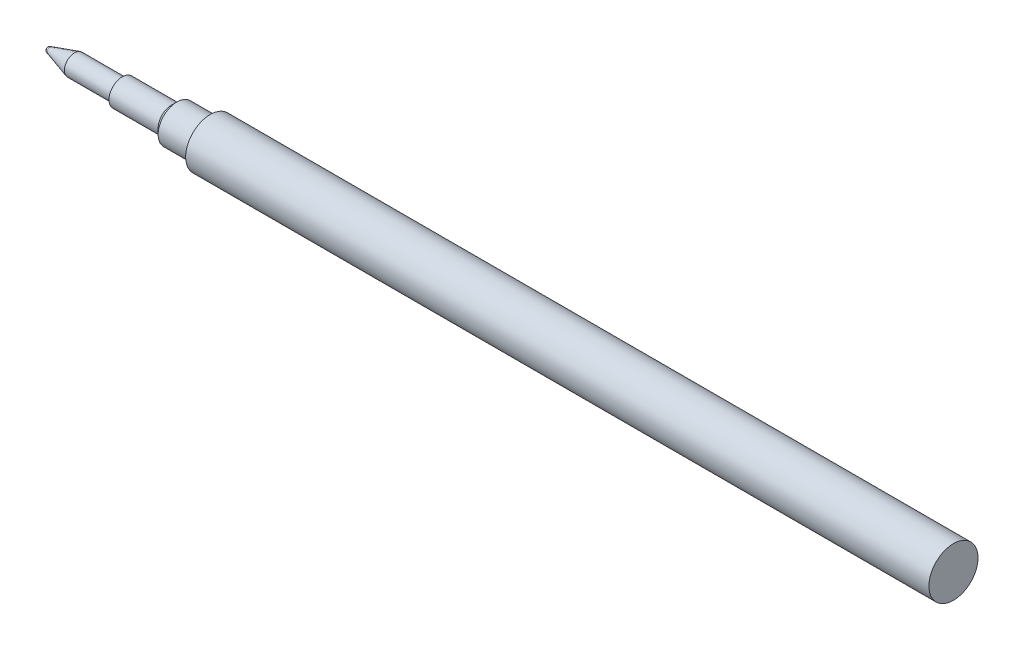
SolidWorks part; units mm, degrees
ref_plane "Front Plane" through (0, 0, 0) normal (0, 0, 1) x (1, 0, 0)
ref_plane "Top Plane" through (0, 0, 0) normal (0, 1, 0) x (1, 0, 0)
ref_plane "Right Plane" through (0, 0, 0) normal (1, 0, 0) x (0, 0, -1)
sketch "Sketch1" plane through (0, 0, 0) normal (0, 0, 1) x (1, 0, 0)
  line L0 (-90.77, 0) -> (-94.83, 0)
  line L1 (0, 0) -> (-90.77, 0)
  line L2 (0, 0) -> (0, 3)
  line L3 (0, 3) -> (-90.77, 3)
  line L4 (-90.77, 0) -> (-90.77, 3)
  line L5 (-94.83, 0) -> (-94.83, 2.3)
  line L6 (-94.83, 2.3) -> (-90.77, 2.3)
  line L7 (-94.83, 0) -> (-95.51, 0)
  line L8 (-95.51, 0) -> (-95.51, 1.62)
  line L9 (-95.51, 1.62) -> (-94.83, 2.3)
  line L10 (-95.51, 0) -> (-101.51, 0)
  line L11 (-101.51, 0) -> (-101.51, 1.62)
  line L12 (-101.51, 1.62) -> (-95.51, 1.62)
  line L13 (-101.51, 0) -> (-107.33, 0)
  line L14 (-107.33, 0) -> (-107.33, 1.25)
  line L15 (-107.33, 1.25) -> (-101.51, 1.25)
  line L16 (-107.33, 1.25) -> (-110.33, 0.35)
  line L17 (-110.33, 0.35) -> (-110.33, 0)
  line L18 (-110.33, 0) -> (-107.33, 0)
  line L19 (-110.33, 0) -> (-110.68, 0)
  arc A0 (-110.68, 0) -> (-110.33, 0.35) centre (-110.33, 0) cw
  dimension "D1" = 3
  dimension "D2" = 90.77
  dimension "D3" = 2.3
  dimension "D4" = 4.06
  dimension "D5" = 0.68
  dimension "D6" = 45
  dimension "D7" = 6
  dimension "D8" = 1.25
  dimension "D9" = 5.82
  dimension "D10" = 3
  dimension "D11" = 0.35
  dimension "D12" = 0.35
revolve "Revolve1" add sketch "Sketch1" angle 360 about L1 region at (-45.385, 1.5, 0) region at (-92.8, 1.15, 0) region at (-95.1503, 0.9898, 0) region at (-98.51, 0.81, 0) region at (-104.42, 0.625, 0) region at (-108.5487, 0.4422, 0) region at (-110.4785, 0.1485, 0)
